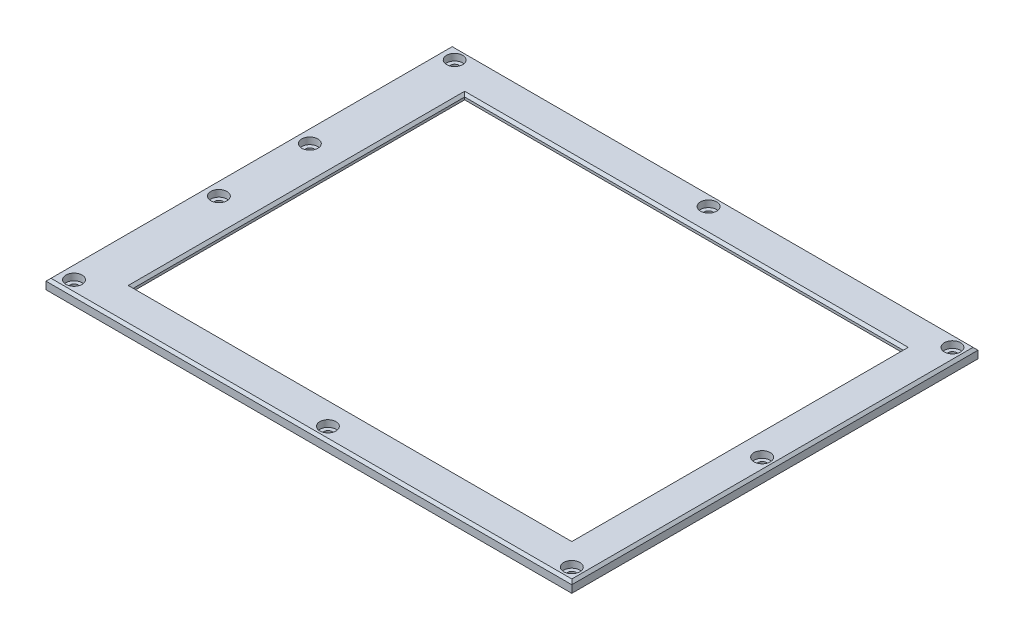
SolidWorks part; units mm, degrees
ref_plane "Front Plane" through (0, 0, 0) normal (0, 0, 1) x (1, 0, 0)
ref_plane "Top Plane" through (0, 0, 0) normal (0, 1, 0) x (1, 0, 0)
ref_plane "Right Plane" through (0, 0, 0) normal (1, 0, 0) x (0, 0, -1)
sketch "Sketch1" plane through (0, 0, 0) normal (0, 1, 0) x (1, 0, 0)
  line L1 (-88, -66.5) -> (88, -66.5)
  line L2 (-88, -66.5) -> (-88, 66.5)
  line L3 (-88, 66.5) -> (88, 66.5)
  line L4 (88, -66.5) -> (88, 66.5)
  line L5 (-88, -66.5) -> (88, 66.5) construction
  line L6 (-88, 66.5) -> (88, -66.5) construction
  line L7 (-108, -81.5) -> (103, -81.5)
  line L8 (-108, -81.5) -> (-108, 81.5)
  line L9 (-108, 81.5) -> (103, 81.5)
  line L10 (103, -81.5) -> (103, 81.5)
  point P0 (0, 0)
  point P6 (0, 0)
  dimension "D1" = 133
  dimension "D2" = 176
  dimension "D3" = 15
  dimension "D4" = 20
  dimension "D5" = 15
  dimension "D6" = 15
extrude "Boss-Extrude1" add sketch "Sketch1" along normal blind 4 contours L8 L7 L10 L9 | L2 L1 L4 L3
sketch "Sketch2" plane through (0, 4, 0) normal (0, 1, 0) x (1, 0, 0)
  line L0 (-108, -81.5) -> (-108, 81.5) construction
  line L1 (-95.75, -71.25) -> (92.75, -71.25)
  line L2 (-95.75, -71.25) -> (-95.75, -10.25)
  line L3 (-95.75, 71.25) -> (92.75, 71.25)
  line L4 (92.75, -71.25) -> (92.75, 71.25)
  line L7 (-95.75, 10.25) -> (-102.25, 10.25)
  line L9 (-95.75, -10.25) -> (-102.25, -10.25)
  line L10 (-102.25, 10.25) -> (-102.25, 6.75)
  line L11 (-102.25, 6.75) -> (-108, 6.75)
  line L13 (-102.25, -6.75) -> (-108, -6.75)
  line L14 (-108, 6.75) -> (-108, -6.75)
  line L15 (-102.25, -6.75) -> (-102.25, -10.25)
  line L16 (-95.75, 10.25) -> (-95.75, 71.25)
  line L17 (-102.25, 10.25) -> (-102.25, -10.25) construction
  line L23 (88, -66.5) -> (88, 66.5) construction
  line L24 (-88, -66.5) -> (88, -66.5) construction
  point P0 (0, 0)
  point P10 (-108, 0)
  point P17 (-102.25, 0)
  point P18 (92.75, 0)
  dimension "D1" = 188.5
  dimension "D2" = 142.5
  dimension "D3" = 20.5
  dimension "D4" = 6.5
  dimension "D5" = 13.5
  dimension "D6" = 4.75
  dimension "D7" = 4.75
extrude "Cut-Extrude1" cut sketch "Sketch2" along normal blind 2 from surface starting at face at (0, 0, 0)
hole_wizard "CBORE for M3 SHCS1" positions "Sketch5" profile "Sketch6" counterbore size "M3" standard "ANSI Metric" end condition up to next
sketch "Sketch5" plane through (0, 4, 0) normal (0, 1, 0) x (1, 0, 0)
  line L0 (-108, -81.5) -> (103, -81.5) construction
  line L1 (-95.75, -71.25) -> (92.75, -71.25) construction
  line L2 (0, -81.5) -> (0, -71.25) construction
  line L4 (0, 81.5) -> (0, 71.25) construction
  line L5 (-108, 81.5) -> (103, 81.5) construction
  line L6 (92.75, 71.25) -> (-95.75, 71.25) construction
  line L8 (-95.75, -71.25) -> (-95.75, -81.5) construction
  line L10 (-95.75, -71.25) -> (-108, -71.25) construction
  line L11 (-108, -81.5) -> (-108, -6.75) construction
  line L13 (92.75, -71.25) -> (92.75, -81.5) construction
  line L15 (92.75, -71.25) -> (103, -71.25) construction
  line L16 (103, -81.5) -> (103, 81.5) construction
  line L18 (-102.25, -10.25) -> (-95.75, -10.25) construction
  line L19 (-95.75, 10.25) -> (-102.25, 10.25) construction
  point P0 (-101.875, 76.375)
  point P2 (0, 76.375)
  point P4 (97.875, 76.375)
  point P6 (97.875, -76.375)
  point P8 (97.875, 0)
  point P10 (0, -76.375)
  point P12 (-101.875, -76.375)
  point P14 (-101.875, -18.25)
  point P16 (-101.875, 18.25)
  point P65 (-101.875, -71.25)
  point P79 (97.875, -71.25)
  dimension "D1" = 8
  dimension "D2" = 8
sketch "Sketch6" plane through (-101.875, 4, -76.375) normal (1, 0, 0) x (0, 0, 1)
  line L0 (0, 0) -> (0, 4)
  line L1 (0, 4) -> (1.7, 4)
  line L3 (1.7, 4) -> (1.7, 2.68)
  line L4 (1.7, 2.68) -> (3.25, 2.68)
  line L5 (3.25, 2.68) -> (3.25, 0)
  line L7 (3.25, 0) -> (0, 0)
  line L11 (0, -6.35) -> (0, 107.95) construction
  dimension "Thru Hole Dia." = 3.4
  dimension "Thru Hole Depth" = 4
  dimension "C'Bore Dia." = 6.5
  dimension "C'Bore Depth" = 2.68
chamfer "Chamfer2" distance 1 angle 45 8 edges at (-88, 4, 0) (0, 4, 66.5) (88, 4, 0) (0, 4, -66.5) (-108, 4, 0) (-2.5, 4, -81.5) (103, 4, 0) (-2.5, 4, 81.5)
